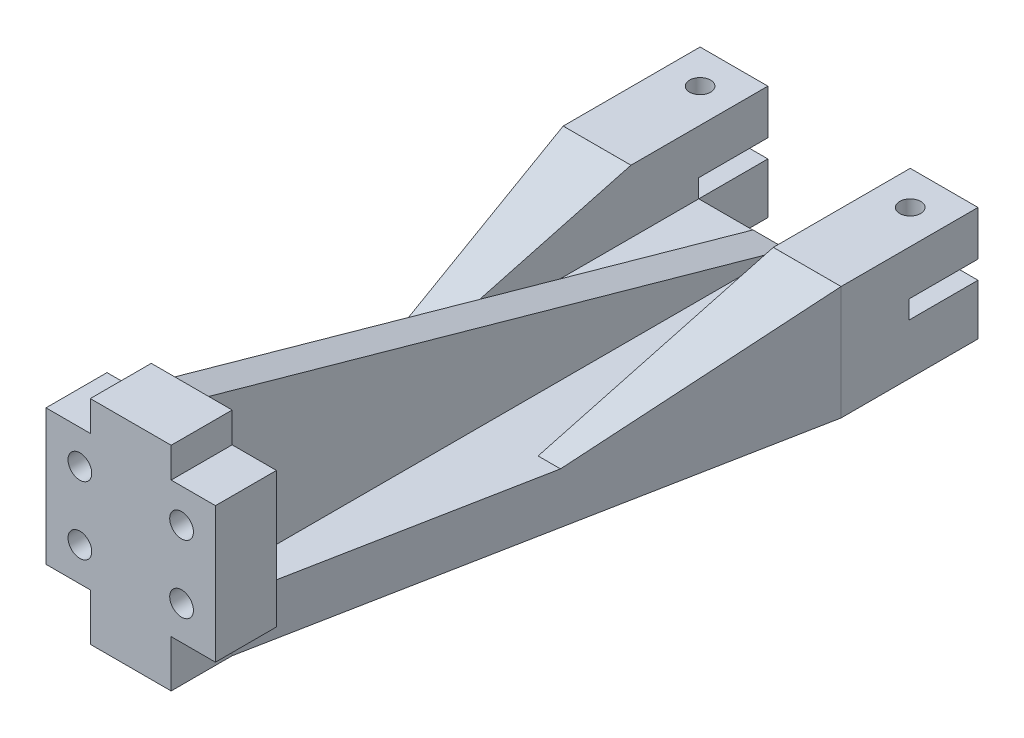
SolidWorks part; units mm, degrees
ref_plane "Front Plane" through (0, 0, 0) normal (0, 0, 1) x (1, 0, 0)
ref_plane "Top Plane" through (0, 0, 0) normal (0, 1, 0) x (1, 0, 0)
ref_plane "Right Plane" through (0, 0, 0) normal (1, 0, 0) x (0, 0, -1)
sketch "Sketch1" plane through (0, 0, 0) normal (0, 1, 0) x (1, 0, 0)
  line L1 (0, 0) -> (41, 0)
  line L2 (0, 0) -> (0, 100.5)
  line L3 (0, 100.5) -> (41, 100.5)
  line L4 (41, 0) -> (41, 100.5)
  dimension "D1" = 41
  dimension "D2" = 100.5
extrude "Boss-Extrude1" add sketch "Sketch1" along normal blind 5
sketch "Sketch2" plane through (0, 5, 0) normal (0, 1, 0) x (1, 0, 0)
  line L1 (0, 100.5) -> (10, 100.5) construction
  line L2 (0, 100.5) -> (0, 90.3) construction
  line L3 (0, 90.3) -> (10, 90.3) construction
  line L4 (10, 100.5) -> (10, 90.3) construction
  line L5 (41, 100.5) -> (31, 100.5) construction
  line L6 (41, 100.5) -> (41, 90.3) construction
  line L7 (41, 90.3) -> (31, 90.3) construction
  line L8 (31, 100.5) -> (31, 90.3) construction
  line L9 (10, 100.5) -> (31, 100.5)
  line L10 (10, 100.5) -> (10, 90.3)
  line L11 (10, 90.3) -> (31, 90.3)
  line L12 (31, 100.5) -> (31, 90.3)
  dimension "D1" = 10.2
  dimension "D3" = 10
  dimension "D4" = 10
extrude "Cut-Extrude1" cut sketch "Sketch2" against normal through all
sketch "Sketch9" plane through (0, 5, 0) normal (0, 1, 0) x (1, 0, 0)
  line L1 (0, 100.5) -> (5, 100.5) construction
  line L2 (0, 100.5) -> (0, 95.5) construction
  line L3 (0, 95.5) -> (5, 95.5) construction
  line L4 (5, 100.5) -> (5, 95.5) construction
  line L5 (31, 100.5) -> (36, 100.5) construction
  line L6 (31, 100.5) -> (31, 95.5) construction
  line L7 (31, 95.5) -> (36, 95.5) construction
  line L8 (36, 100.5) -> (36, 95.5) construction
  circle A0 centre (5, 95.5) radius 1.75
  circle A1 centre (36, 95.5) radius 1.75
  dimension "D3" = 3.5
  dimension "D4" = 3.5
  dimension "D1" = 5
  dimension "D2" = 5
extrude "Cut-Extrude4" cut sketch "Sketch9" against normal through all
sketch "Sketch11" plane through (0, 5, 0) normal (0, 1, 0) x (1, 0, 0)
  line L0 (20.5, 90.3) -> (20.5, 0) construction
  line L1 (10, 90.3) -> (31, 90.3) construction
  line L2 (0, 0) -> (41, 0) construction
  line L3 (15.5, 0) -> (25.5, 0) construction
  line L4 (15.5, 0) -> (0, 80.3)
  line L5 (0, 100.5) -> (0, 0) construction
  line L6 (25.5, 0) -> (41, 80.3)
  line L7 (41, 0) -> (41, 100.5) construction
  line L8 (0, 80.3) -> (0, 0)
  line L9 (0, 0) -> (15.5, 0)
  line L10 (41, 80.3) -> (41, 0)
  line L11 (41, 0) -> (25.5, 0)
  point P8 (20.5, 0)
  dimension "D1" = 10
  dimension "D2" = 10
extrude "Cut-Extrude5" cut sketch "Sketch11" against normal through all
sketch "Slider Reference" plane through (0, 0, 0) normal (0, 0, 1) x (1, 0, 0)
  line L0 (15.5, 0) -> (25.5, 0) construction
  line L1 (8, 0) -> (33, 0) construction
  line L2 (8, 0) -> (8, 28.9) construction
  line L3 (8, 28.9) -> (33, 28.9) construction
  line L4 (33, 0) -> (33, 28.9) construction
  line L6 (13, 19.45) -> (28, 19.45) construction
  line L7 (13, 19.45) -> (13, 9.45) construction
  line L8 (13, 9.45) -> (28, 9.45) construction
  line L9 (28, 19.45) -> (28, 9.45) construction
  line L10 (8, 24.45) -> (33, 24.45) construction
  line L11 (8, 24.45) -> (8, 4.45) construction
  line L12 (8, 4.45) -> (33, 4.45) construction
  line L13 (33, 24.45) -> (33, 4.45) construction
  point P5 (20.5, 0)
  point P8 (20.5, 0)
  point P13 (13, 14.45)
  point P14 (8, 14.45)
  point P15 (20.5, 19.45)
  point P16 (20.5, 28.9)
  dimension "D1" = 28.9
  dimension "D2" = 25
  dimension "D3" = 10
  dimension "D4" = 15
  dimension "D5" = 5
  dimension "D6" = 5
sketch "Sketch12" plane through (0, 5, 0) normal (0, 1, 0) x (1, 0, 0)
  line L0 (25.5, 0) -> (15.5, 0)
  line L1 (15.5, 0) -> (14.5349, 5)
  line L2 (15.5, 0) -> (0, 80.3) construction
  line L3 (14.5349, 5) -> (26.4651, 5)
  line L4 (41, 80.3) -> (25.5, 0) construction
  line L5 (26.4651, 5) -> (25.5, 0)
  dimension "D1" = 5
extrude "Boss-Extrude4" add sketch "Sketch12" along normal up to vertex (23.9 mm away) up to point (8, 28.9, 0)
sketch "Sketch16" plane through (0, 5, 0) normal (0, 1, 0) x (1, 0, 0)
  line L0 (10, 90.3) -> (31, 90.3) construction
  line L1 (18, 90.3) -> (23, 90.3)
  line L2 (18, 90.3) -> (18, 5)
  line L3 (18, 5) -> (23, 5)
  line L4 (23, 90.3) -> (23, 5)
  line L5 (26.4651, 5) -> (14.5349, 5) construction
  point P6 (20.5, 90.3)
  point P7 (20.5, 90.3)
  dimension "D1" = 5
extrude "Boss-Extrude5" add sketch "Sketch16" along normal up to surface (23.9 mm away) up to face at (20.5, 28.9, -2.5)
sketch "Sketch17" plane through (18, 0, 0) normal (-1, 0, 0) x (0, 0, 1)
  line L0 (-90.4, 5) -> (-5, 28.9)
  line L1 (-100.5, 5) -> (-80.3, 5) construction
  line L2 (-5, 28.9) -> (-90.3, 28.9)
  line L3 (-90.3, 28.9) -> (-90.4, 5)
  line L4 (-90.3, 28.9) -> (-90.3, 5) construction
extrude "Cut-Extrude8" cut sketch "Sketch17" against normal through all
sketch "Sketch23" plane through (0, 28.9, 0) normal (0, 1, 0) x (1, 0, 0)
  line L0 (26.4651, 5) -> (33, 5)
  line L1 (33, 5) -> (33, 0)
  line L2 (8, 0) -> (33, 0) construction
  line L3 (33, 0) -> (25.5, 0)
  line L4 (25.5, 0) -> (26.4651, 5)
  line L5 (14.5349, 5) -> (8, 5)
  line L6 (8, 5) -> (8, 0)
  line L7 (8, 0) -> (33, 0) construction
  line L8 (8, 0) -> (15.5, 0)
  line L9 (15.5, 0) -> (14.5349, 5)
extrude "Boss-Extrude6" add sketch "Sketch23" against normal up to surface (28.9 mm away) up to face at (20.5, 0, -74.32)
sketch "Sketch25" plane through (0, 0, -5) normal (0, 0, -1) x (-1, 0, 0)
  line L0 (-8, 4.45) -> (-33, 4.45) construction
  line L1 (-8, 4.45) -> (-14.5349, 4.45)
  line L3 (-8, 4.45) -> (-8, 0)
  line L4 (-8, 0) -> (-14.5349, 0)
  line L6 (-14.5349, 4.45) -> (-14.5349, 0)
  line L8 (-26.4651, 0) -> (-33, 0)
  line L9 (-26.4651, 0) -> (-26.4651, 4.45)
  line L10 (-26.4651, 4.45) -> (-33, 4.45)
  line L11 (-33, 0) -> (-33, 4.45)
  line L12 (-8, 24.45) -> (-33, 24.45) construction
  line L13 (-8, 28.9) -> (-14.5349, 28.9)
  line L14 (-8, 28.9) -> (-8, 24.45)
  line L15 (-8, 24.45) -> (-14.5349, 24.45)
  line L16 (-14.5349, 28.9) -> (-14.5349, 24.45)
  line L18 (-33, 28.9) -> (-26.4651, 28.9)
  line L19 (-33, 28.9) -> (-33, 24.45)
  line L20 (-33, 24.45) -> (-26.4651, 24.45)
  line L21 (-26.4651, 28.9) -> (-26.4651, 24.45)
extrude "Cut-Extrude9" cut sketch "Sketch25" against normal through all
sketch "Sketch26" plane through (0, 0, 0) normal (0, 0, 1) x (1, 0, 0)
  circle A0 centre (13, 19.45) radius 1.75
  circle A1 centre (28, 19.45) radius 1.75
  circle A2 centre (13, 9.45) radius 1.75
  circle A3 centre (28, 9.45) radius 1.75
  dimension "D1" = 3.5
extrude "Cut-Extrude10" cut sketch "Sketch26" against normal through all
sketch "Sketch27" plane through (0, 0, 0) normal (0, -1, 0) x (1, 0, 0)
  line L12 (26.4651, -5) -> (26.4651, 0)
  line L13 (26.4651, 0) -> (14.5349, 0)
  line L14 (14.5349, 0) -> (14.5349, -5)
  line L15 (14.5349, -5) -> (0, -80.3)
  line L16 (0, -80.3) -> (0, -100.5)
  line L17 (0, -100.5) -> (10, -100.5)
  line L18 (10, -100.5) -> (10, -90.3)
  line L19 (10, -90.3) -> (31, -90.3)
  line L20 (31, -90.3) -> (31, -100.5)
  line L21 (31, -100.5) -> (41, -100.5)
  line L22 (41, -100.5) -> (41, -80.3)
  line L23 (41, -80.3) -> (26.4651, -5)
  line L24 (26.4651, -5) -> (26.4651, 0)
  line L25 (26.4651, 0) -> (14.5349, 0)
  line L26 (14.5349, 0) -> (14.5349, -5)
  line L27 (14.5349, -5) -> (0, -80.3)
  line L28 (0, -80.3) -> (0, -100.5)
  line L29 (0, -100.5) -> (10, -100.5)
  line L30 (10, -100.5) -> (10, -90.3)
  line L31 (10, -90.3) -> (31, -90.3)
  line L32 (31, -90.3) -> (31, -100.5)
  line L33 (31, -100.5) -> (41, -100.5)
  line L34 (41, -100.5) -> (41, -80.3)
  line L35 (41, -80.3) -> (26.4651, -5)
  circle A0 centre (5, -95.5) radius 1.75 construction
  circle A1 centre (36, -95.5) radius 1.75 construction
  circle A2 centre (5, -95.5) radius 1.75
  circle A3 centre (36, -95.5) radius 1.75
  dimension "D1" = 0
extrude "Boss-Extrude7" add sketch "Sketch27" along normal blind 2.5
sketch "Sketch28" plane through (0, 0, 0) normal (0, 0, 1) x (1, 0, 0)
  line L12 (26.4651, -2.5) -> (26.4651, 4.45)
  line L13 (26.4651, 4.45) -> (33, 4.45)
  line L14 (33, 4.45) -> (33, 24.45)
  line L15 (33, 24.45) -> (26.4651, 24.45)
  line L16 (26.4651, 24.45) -> (26.4651, 28.9)
  line L17 (26.4651, 28.9) -> (14.5349, 28.9)
  line L18 (14.5349, 28.9) -> (14.5349, 24.45)
  line L19 (14.5349, 24.45) -> (8, 24.45)
  line L20 (8, 24.45) -> (8, 4.45)
  line L21 (8, 4.45) -> (14.5349, 4.45)
  line L22 (14.5349, 4.45) -> (14.5349, -2.5)
  line L23 (14.5349, -2.5) -> (26.4651, -2.5)
  line L24 (26.4651, -2.5) -> (26.4651, 4.45)
  line L25 (26.4651, 4.45) -> (33, 4.45)
  line L26 (33, 4.45) -> (33, 24.45)
  line L27 (33, 24.45) -> (26.4651, 24.45)
  line L28 (26.4651, 24.45) -> (26.4651, 28.9)
  line L29 (26.4651, 28.9) -> (14.5349, 28.9)
  line L30 (14.5349, 28.9) -> (14.5349, 24.45)
  line L31 (14.5349, 24.45) -> (8, 24.45)
  line L32 (8, 24.45) -> (8, 4.45)
  line L33 (8, 4.45) -> (14.5349, 4.45)
  line L34 (14.5349, 4.45) -> (14.5349, -2.5)
  line L35 (14.5349, -2.5) -> (26.4651, -2.5)
  circle A0 centre (28, 9.45) radius 1.75 construction
  circle A1 centre (13, 9.45) radius 1.75 construction
  circle A2 centre (28, 19.45) radius 1.75 construction
  circle A3 centre (13, 19.45) radius 1.75 construction
  circle A4 centre (28, 9.45) radius 1.75
  circle A5 centre (13, 9.45) radius 1.75
  circle A6 centre (28, 19.45) radius 1.75
  circle A7 centre (13, 19.45) radius 1.75
  dimension "D1" = 0
extrude "Boss-Extrude8" add sketch "Sketch28" along normal blind 4
sketch "Sketch29" plane through (0, 5, 0) normal (0, 1, 0) x (1, 0, 0)
  line L1 (41, 80.3) -> (31, 80.3)
  line L2 (41, 80.3) -> (41, 90.3)
  line L3 (41, 90.3) -> (31, 90.3)
  line L4 (31, 80.3) -> (31, 90.3)
  line L5 (0, 80.3) -> (10, 80.3)
  line L6 (0, 80.3) -> (0, 90.3)
  line L7 (0, 90.3) -> (10, 90.3)
  line L8 (10, 80.3) -> (10, 90.3)
extrude "Boss-Extrude9" add sketch "Sketch29" along normal blind 2.7
sketch "Sketch30" plane through (0, 7.7, 0) normal (0, 1, 0) x (1, 0, 0)
  line L1 (0, 80.3) -> (10, 80.3)
  line L2 (0, 80.3) -> (0, 100.5)
  line L3 (0, 100.5) -> (10, 100.5)
  line L4 (10, 80.3) -> (10, 100.5)
  line L5 (31, 80.3) -> (41, 80.3)
  line L6 (31, 80.3) -> (31, 100.5)
  line L7 (31, 100.5) -> (41, 100.5)
  line L8 (41, 80.3) -> (41, 100.5)
extrude "Boss-Extrude10" add sketch "Sketch30" along normal blind 6.6
sketch "Sketch31" plane through (0, 14.3, 0) normal (0, 1, 0) x (1, 0, 0)
  circle A4 centre (36, 95.5) radius 1.55
  circle A5 centre (5, 95.5) radius 1.55
  dimension "D1" = 3.1
  dimension "D2" = 3.1
extrude "Cut-Extrude11" cut sketch "Sketch31" against normal up to surface (6.6 mm away) up to face at (36, 7.7, -95.4)
chamfer "Chamfer2" distance 34.7 angle 15 2 edges at (5, 5, -80.3) (36, 5, -80.3) first distance on face at (11.7558, 5, -58.5333) first distance on face at (29.2442, 5, -58.5333)
